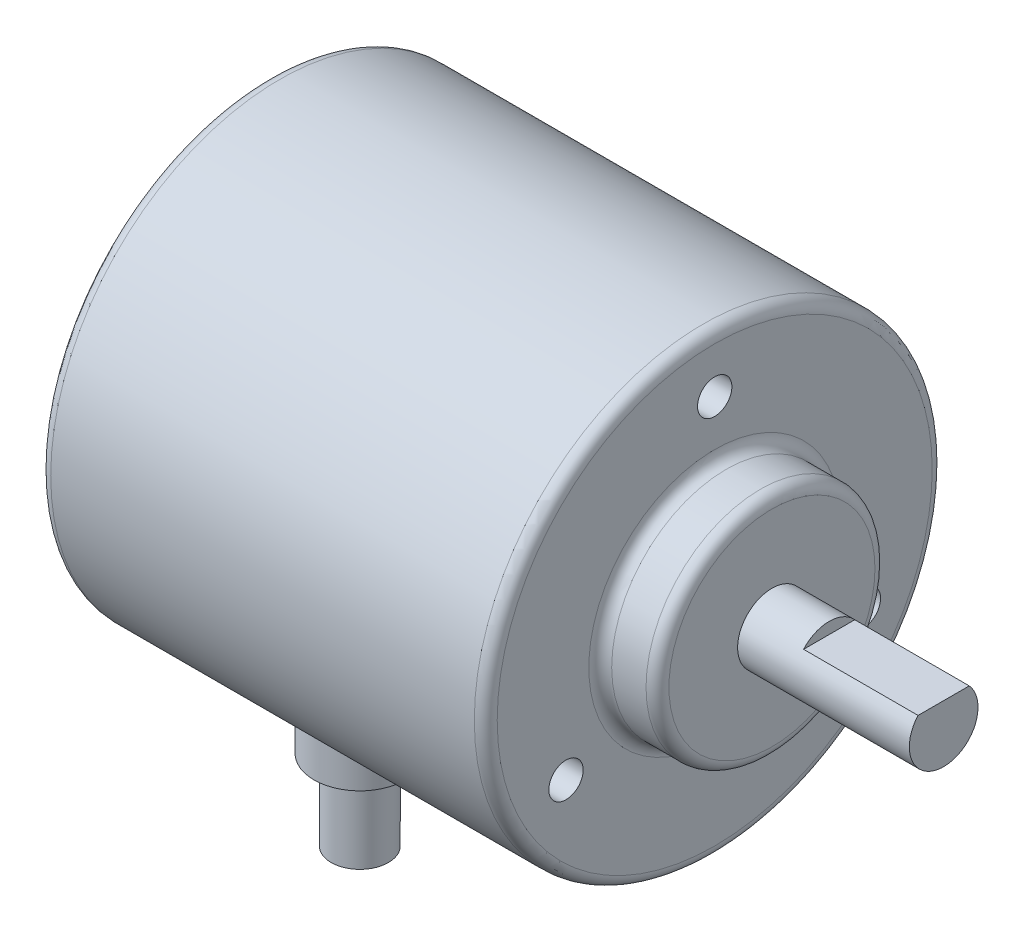
SolidWorks part; units mm, degrees
ref_plane "Front Plane" through (0, 0, 0) normal (0, 0, 1) x (1, 0, 0)
ref_plane "Top Plane" through (0, 0, 0) normal (0, 1, 0) x (1, 0, 0)
ref_plane "Right Plane" through (0, 0, 0) normal (1, 0, 0) x (0, 0, -1)
sketch "Sketch2" plane through (0, 0, 0) normal (1, 0, 0) x (0, 0, -1)
  circle A0 centre (0, 0) radius 20
  dimension "D1" = 40
extrude "Boss-Extrude1" add sketch "Sketch2" along normal blind 39
sketch "Sketch3" plane through (39, 0, 0) normal (1, 0, 0) x (0, 0, -1)
  circle A0 centre (0, 0) radius 10
  dimension "D1" = 20
extrude "Boss-Extrude2" add sketch "Sketch3" along normal blind 5
sketch "Sketch4" plane through (44, 0, 0) normal (1, 0, 0) x (0, 0, -1)
  circle A0 centre (0, 0) radius 3
  dimension "D1" = 6
extrude "Boss-Extrude3" add sketch "Sketch4" along normal blind 15
sketch "Sketch5" plane through (59, 0, 0) normal (1, 0, 0) x (0, 0, -1)
  line L0 (-3, 0) -> (3, 0) construction
  line L1 (-2.2361, 2) -> (2.2361, 2)
  line L2 (-3, 2) -> (3, 2) construction
  arc A1 (2.2361, 2) -> (-2.2361, 2) centre (0, 0) ccw
  dimension "D2" = 3
  dimension "D1" = 2
extrude "Cut-Extrude1" cut sketch "Sketch5" against normal blind 10
sketch "Sketch6" plane through (39, 0, 0) normal (1, 0, 0) x (0, 0, -1)
  circle A0 centre (0, 0) radius 15 construction
  circle A1 centre (0, 15) radius 1.5
  circle A2 centre (12.9904, -7.5) radius 1.5
  circle A3 centre (-12.9904, -7.5) radius 1.5
  point P12 (0, 0)
  dimension "D1" = 30
  dimension "D2" = 3
  dimension "D4" = 12.9904
  dimension "D5" = 7.5
  dimension "D3" = 3
extrude "Cut-Extrude2" cut sketch "Sketch6" against normal blind 7
sketch3d "3DSketch1" plane through (0, 0, 0) normal (0, 0, 1) x (1, 0, 0)
  dimension "D1" = 20
sketch "Sketch8" plane through (0, -20, 0) normal (0, 1, 0) x (1, 0, 0)
  line L0 (0, 0) -> (39, 0) construction
  line L1 (39, -10) -> (39, 10) construction
  line L2 (0, 20) -> (0, -20) construction
  circle A0 centre (8, 0) radius 4
  dimension "D2" = 8
  dimension "D1" = 8
extrude "Boss-Extrude4" add sketch "Sketch8" along normal up to surface and the other way blind 7.5 up to face at (39, 0, -20)
sketch "Sketch9" plane through (0, -27.5, 0) normal (0, -1, 0) x (1, 0, 0)
  circle A0 centre (8, 0) radius 2.5
  dimension "D1" = 5
extrude "Boss-Extrude5" add sketch "Sketch9" along normal blind 7
fillet "Fillet1" radius 1 6 edges at (0, 0, -20) (39, 0, -20) (8.8315, -19.6136, 3.9126) (8, -27.5, 2.5) (39, 0, -10) (44, 0, -10)
